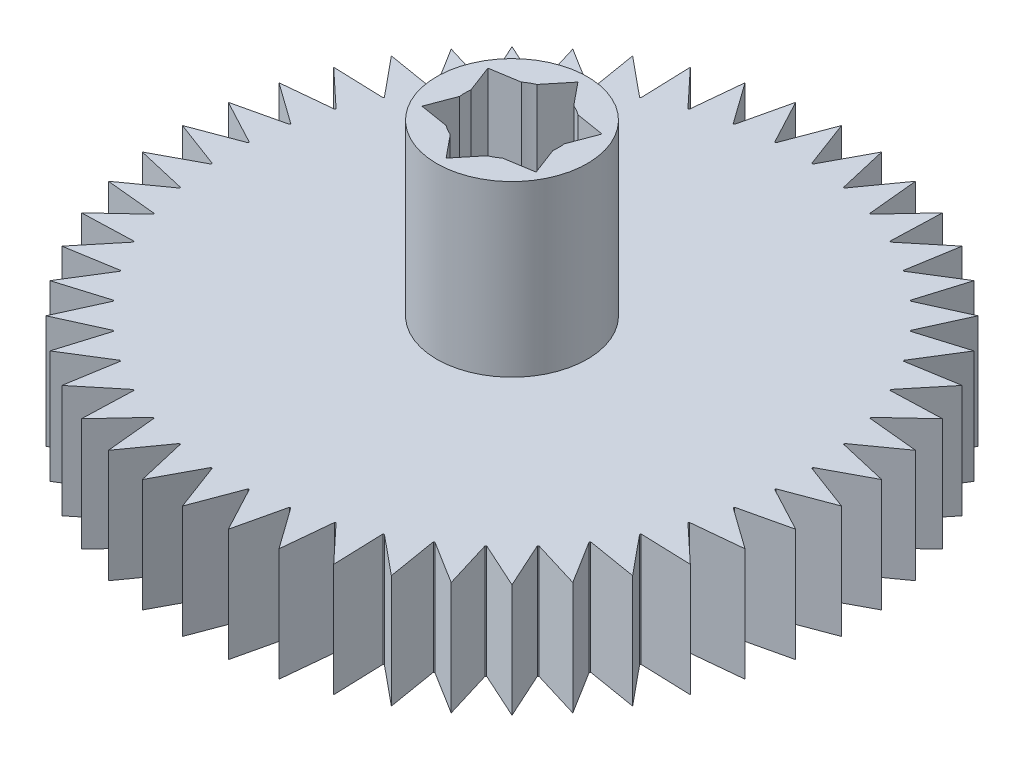
SolidWorks part; units mm, degrees
ref_plane "Спереди" through (0, 0, 0) normal (0, 0, 1) x (1, 0, 0)
ref_plane "Сверху" through (0, 0, 0) normal (0, 1, 0) x (1, 0, 0)
ref_plane "Справа" through (0, 0, 0) normal (1, 0, 0) x (0, 0, -1)
sketch "Эскиз1" plane through (0, 0, 0) normal (0, 1, 0) x (1, 0, 0)
  line L0 (2.2842, 17.3503) -> (2.8954, 14.7179)
  line L1 (1.0126, 14.9658) -> (2.2842, 17.3503)
  line L2 (4.5293, 16.9037) -> (4.7917, 14.2141)
  line L3 (2.9573, 14.7056) -> (4.5293, 16.9037)
  line L4 (0, 1.5) -> (2.2, 1.5)
  line L5 (0, 1.5) -> (-2.2, 1.5)
  line L6 (0, -1.5) -> (-2.2, -1.5)
  line L7 (0, -1.5) -> (2.2, -1.5)
  line L299 (6.697, 16.1679) -> (6.606, 13.467)
  line L303 (4.8515, 14.1938) -> (6.697, 16.1679)
  line L304 (0, 17.5) -> (0.9495, 14.9699)
  line L305 (-0.9495, 14.9699) -> (0, 17.5)
  line L306 (8.75, 15.1554) -> (8.3073, 12.4896)
  line L307 (6.6626, 13.4391) -> (8.75, 15.1554)
  line L308 (10.6533, 13.8837) -> (9.8664, 11.2984)
  line L309 (8.3598, 12.4545) -> (10.6533, 13.8837)
  line L310 (12.3744, 12.3744) -> (11.2567, 9.9139)
  line L311 (9.9139, 11.2567) -> (12.3744, 12.3744)
  line L312 (13.8837, 10.6533) -> (12.4545, 8.3598)
  line L313 (11.2984, 9.8664) -> (13.8837, 10.6533)
  line L314 (15.1554, 8.75) -> (13.4391, 6.6626)
  line L315 (12.4896, 8.3073) -> (15.1554, 8.75)
  line L316 (16.1679, 6.697) -> (14.1938, 4.8515)
  line L317 (13.467, 6.606) -> (16.1679, 6.697)
  line L318 (16.9037, 4.5293) -> (14.7056, 2.9573)
  line L319 (14.2141, 4.7917) -> (16.9037, 4.5293)
  line L320 (17.3503, 2.2842) -> (14.9658, 1.0126)
  line L321 (14.7179, 2.8954) -> (17.3503, 2.2842)
  line L322 (17.5, 0) -> (14.9699, -0.9495)
  line L323 (14.9699, 0.9495) -> (17.5, 0)
  line L324 (17.3503, -2.2842) -> (14.7179, -2.8954)
  line L325 (14.9658, -1.0126) -> (17.3503, -2.2842)
  line L326 (16.9037, -4.5293) -> (14.2141, -4.7917)
  line L327 (14.7056, -2.9573) -> (16.9037, -4.5293)
  line L328 (16.1679, -6.697) -> (13.467, -6.606)
  line L329 (14.1938, -4.8515) -> (16.1679, -6.697)
  line L330 (15.1554, -8.75) -> (12.4896, -8.3073)
  line L331 (13.4391, -6.6626) -> (15.1554, -8.75)
  line L332 (13.8837, -10.6533) -> (11.2984, -9.8664)
  line L333 (12.4545, -8.3598) -> (13.8837, -10.6533)
  line L334 (12.3744, -12.3744) -> (9.9139, -11.2567)
  line L335 (11.2567, -9.9139) -> (12.3744, -12.3744)
  line L336 (10.6533, -13.8837) -> (8.3598, -12.4545)
  line L337 (9.8664, -11.2984) -> (10.6533, -13.8837)
  line L338 (8.75, -15.1554) -> (6.6626, -13.4391)
  line L339 (8.3073, -12.4896) -> (8.75, -15.1554)
  line L340 (6.697, -16.1679) -> (4.8515, -14.1938)
  line L341 (6.606, -13.467) -> (6.697, -16.1679)
  line L342 (4.5293, -16.9037) -> (2.9573, -14.7056)
  line L343 (4.7917, -14.2141) -> (4.5293, -16.9037)
  line L344 (2.2842, -17.3503) -> (1.0126, -14.9658)
  line L345 (2.8954, -14.7179) -> (2.2842, -17.3503)
  line L346 (0, -17.5) -> (-0.9495, -14.9699)
  line L347 (0.9495, -14.9699) -> (0, -17.5)
  line L348 (-2.2842, -17.3503) -> (-2.8954, -14.7179)
  line L349 (-1.0126, -14.9658) -> (-2.2842, -17.3503)
  line L350 (-4.5293, -16.9037) -> (-4.7917, -14.2141)
  line L351 (-2.9573, -14.7056) -> (-4.5293, -16.9037)
  line L352 (-6.697, -16.1679) -> (-6.606, -13.467)
  line L353 (-4.8515, -14.1938) -> (-6.697, -16.1679)
  line L354 (-8.75, -15.1554) -> (-8.3073, -12.4896)
  line L355 (-6.6626, -13.4391) -> (-8.75, -15.1554)
  line L356 (-10.6533, -13.8837) -> (-9.8664, -11.2984)
  line L357 (-8.3598, -12.4545) -> (-10.6533, -13.8837)
  line L358 (-12.3744, -12.3744) -> (-11.2567, -9.9139)
  line L359 (-9.9139, -11.2567) -> (-12.3744, -12.3744)
  line L360 (-13.8837, -10.6533) -> (-12.4545, -8.3598)
  line L361 (-11.2984, -9.8664) -> (-13.8837, -10.6533)
  line L362 (-15.1554, -8.75) -> (-13.4391, -6.6626)
  line L363 (-12.4896, -8.3073) -> (-15.1554, -8.75)
  line L364 (-16.1679, -6.697) -> (-14.1938, -4.8515)
  line L365 (-13.467, -6.606) -> (-16.1679, -6.697)
  line L366 (-16.9037, -4.5293) -> (-14.7056, -2.9573)
  line L367 (-14.2141, -4.7917) -> (-16.9037, -4.5293)
  line L368 (-17.3503, -2.2842) -> (-14.9658, -1.0126)
  line L369 (-14.7179, -2.8954) -> (-17.3503, -2.2842)
  line L370 (-17.5, 0) -> (-14.9699, 0.9495)
  line L371 (-14.9699, -0.9495) -> (-17.5, 0)
  line L372 (-17.3503, 2.2842) -> (-14.7179, 2.8954)
  line L373 (-14.9658, 1.0126) -> (-17.3503, 2.2842)
  line L374 (-16.9037, 4.5293) -> (-14.2141, 4.7917)
  line L375 (-14.7056, 2.9573) -> (-16.9037, 4.5293)
  line L376 (-16.1679, 6.697) -> (-13.467, 6.606)
  line L377 (-14.1938, 4.8515) -> (-16.1679, 6.697)
  line L378 (-15.1554, 8.75) -> (-12.4896, 8.3073)
  line L379 (-13.4391, 6.6626) -> (-15.1554, 8.75)
  line L380 (-13.8837, 10.6533) -> (-11.2984, 9.8664)
  line L381 (-12.4545, 8.3598) -> (-13.8837, 10.6533)
  line L382 (-12.3744, 12.3744) -> (-9.9139, 11.2567)
  line L383 (-11.2567, 9.9139) -> (-12.3744, 12.3744)
  line L384 (-10.6533, 13.8837) -> (-8.3598, 12.4545)
  line L385 (-9.8664, 11.2984) -> (-10.6533, 13.8837)
  line L386 (-8.75, 15.1554) -> (-6.6626, 13.4391)
  line L387 (-8.3073, 12.4896) -> (-8.75, 15.1554)
  line L388 (-6.697, 16.1679) -> (-4.8515, 14.1938)
  line L389 (-6.606, 13.467) -> (-6.697, 16.1679)
  line L390 (-4.5293, 16.9037) -> (-2.9573, 14.7056)
  line L391 (-4.7917, 14.2141) -> (-4.5293, 16.9037)
  line L392 (-2.2842, 17.3503) -> (-1.0126, 14.9658)
  line L393 (-2.8954, 14.7179) -> (-2.2842, 17.3503)
  arc A0 (-2.2, 1.5) -> (-2.2, -1.5) centre (1.4803, 0) ccw
  arc A1 (2.2, 1.5) -> (2.2, -1.5) centre (-1.1791, 0) cw
  circle A3 centre (0, 0) radius 15
  point P158 (0, 0)
  point P224 (0, 0)
extrude "Бобышка-Вытянуть5" add sketch "Эскиз1" along normal blind 6 contours A3 | A3 L344 L345 | A3 L342 L343 | A3 L340 L341 | A3 L338 L339 | A3 L336 L337 | A3 L334 L335 | A3 L346 L347 | A3 L348 L349 | A3 L350 L351 | A3 L352 L353 | A3 L354 L355 | A3 L356 L357 | A3 L358 L359 | A3 L360 L361 | A3 L362 L363 | A3 L364 L365 | A3 L366 L367 | A3 L368 L369 | A3 L370 L371 | A3 L372 L373 | A3 L374 L375 | A3 L376 L377 | A3 L378 L379 | A3 L380 L381 | A3 L382 L383 | A3 L384 L385 | A3 L386 L387 | A3 L388 L389 | A3 L390 L391 | A3 L392 L393 | A3 L304 L305 | A3 L0 L1 | A3 L2 L3 | A3 L299 L303 | A3 L306 L307 | A3 L308 L309 | A3 L310 L311 | A3 L312 L313 | A3 L314 L315 | A3 L316 L317 | A3 L318 L319 | A3 L320 L321 | A3 L322 L323 | A3 L324 L325 | A3 L326 L327 | A3 L328 L329 | A3 L330 L331 | A3 L332 L333 region at (2.0658, 0, -15.6913) region at (2.8436, 0, -14.2957) region at (4.0962, 0, -15.2874) region at (0, 0, -15.8267) region at (6.0566, 0, -14.6219) region at (-2.0658, 0, -15.6913) region at (7.9133, 0, -13.7063) region at (-4.0962, 0, -15.2874) region at (9.6347, 0, -12.5561) region at (-6.0566, 0, -14.6219) region at (11.1911, 0, -11.1911) region at (-7.9133, 0, -13.7063) region at (12.5561, 0, -9.6347) region at (-9.6347, 0, -12.5561) region at (13.7063, 0, -7.9133) region at (-11.1911, 0, -11.1911) region at (14.6219, 0, -6.0566) region at (-12.5561, 0, -9.6347) region at (15.2874, 0, -4.0962) region at (-13.7063, 0, -7.9133) region at (15.6913, 0, -2.0658) region at (-14.6219, 0, -6.0566) region at (15.8267, 0, 0) region at (-15.2874, 0, -4.0962) region at (-15.6913, 0, -2.0658) region at (15.6913, 0, 2.0658) region at (-15.8267, 0, 0) region at (15.2874, 0, 4.0962) region at (-15.6913, 0, 2.0658) region at (14.6219, 0, 6.0566) region at (-15.2874, 0, 4.0962) region at (13.7063, 0, 7.9133) region at (-14.6219, 0, 6.0566) region at (12.5561, 0, 9.6347) region at (-13.7063, 0, 7.9133) region at (11.1911, 0, 11.1911) region at (-12.5561, 0, 9.6347) region at (9.6347, 0, 12.5561) region at (-11.1911, 0, 11.1911) region at (7.9133, 0, 13.7063) region at (-9.6347, 0, 12.5561) region at (6.0566, 0, 14.6219) region at (-7.9133, 0, 13.7063) region at (4.0962, 0, 15.2874) region at (-6.0566, 0, 14.6219) region at (2.0658, 0, 15.6913) region at (-4.0962, 0, 15.2874) region at (0, 0, 15.8267) region at (-2.0658, 0, 15.6913)
extrude "Бобышка-Вытянуть6" add sketch "Эскиз1<5>" along normal blind 6 contours L6 A0 L5 L4 A1 L7
sketch "Эскиз1<5>" plane through (0, 0, 0) normal (0, 1, 0) x (1, 0, 0) same geometry as "Эскиз1"
ref_plane "Плоскость3" through (0, 6, 0) normal (0, 1, 0) x (1, 0, 0)
ref_plane "Плоскость4" through (0, 15, 0) normal (0, -1, 0) x (-1, 0, 0)
sketch "Эскиз4" plane through (0, 6, 0) normal (0, 1, 0) x (1, 0, 0)
  circle A0 centre (0, 0) radius 4
ref_plane "Плоскость5" through (0, 0, 0) normal (0, -1, 0) x (-1, 0, 0)
sketch "Эскиз6" plane through (0, 0, 0) normal (0, -1, 0) x (-1, 0, 0)
  circle A0 centre (0, 0) radius 4
extrude "Бобышка-Вытянуть9" add sketch "Эскиз6" along normal blind 5
extrude "Бобышка-Вытянуть10" add sketch "Эскиз4" along normal blind 9
ref_plane "Плоскость6" through (0, 15, 0) normal (0, 1, 0) x (1, 0, 0)
sketch "Эскиз7" plane through (0, 15, 0) normal (0, 1, 0) x (1, 0, 0)
  line L0 (2.4818, 0.3015) -> (3.0311, 1.75)
  line L2 (1.502, 1.9985) -> (3.0311, 1.75)
  line L4 (-0.9798, 2.3) -> (0, 3.5)
  line L5 (0.9798, 2.3) -> (0, 3.5)
  line L6 (1.502, -1.9985) -> (3.0311, -1.75)
  line L7 (2.4818, -0.3015) -> (3.0311, -1.75)
  line L8 (-0.9798, -2.3) -> (0, -3.5)
  line L9 (0.9798, -2.3) -> (0, -3.5)
  line L10 (-2.4818, -0.3015) -> (-3.0311, -1.75)
  line L11 (-1.502, -1.9985) -> (-3.0311, -1.75)
  line L12 (-1.502, 1.9985) -> (-3.0311, 1.75)
  line L13 (-2.4818, 0.3015) -> (-3.0311, 1.75)
  circle A0 centre (0, 0) radius 2.5
  point P23 (0, 0)
  dimension "D1" = 6
extrude "Вырез-Вытянуть1" cut sketch "Эскиз7" against normal blind 6 contours A0 | A0 L12 L13 | A0 L5 L4 | A0 L0 L2 | A0 L6 L7 | A0 L8 L9 | A0 L10 L11 region at (2.4182, 15, -1.3962) region at (0, 15, 0) region at (2.4182, 15, 1.3962) region at (0, 15, -2.7923) region at (0, 15, 2.7923) region at (-2.4182, 15, -1.3962) region at (-2.4182, 15, 1.3962)
